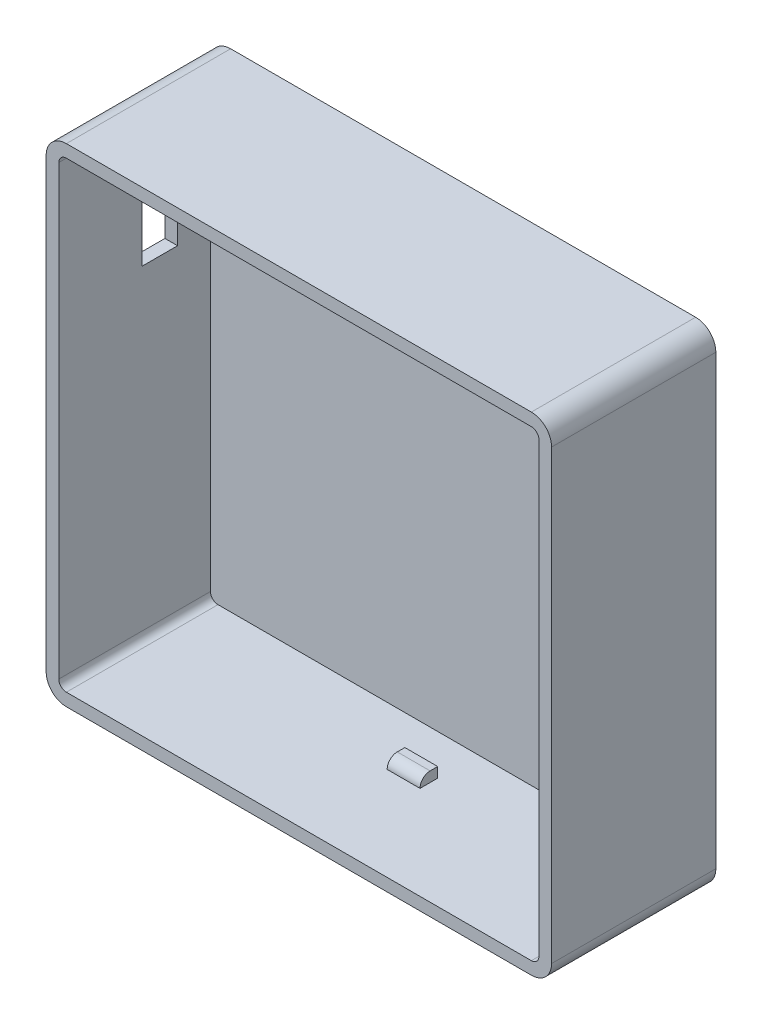
SolidWorks part; units mm, degrees
ref_plane "Front Plane" through (0, 0, 0) normal (0, 0, 1) x (1, 0, 0)
ref_plane "Top Plane" through (0, 0, 0) normal (0, 1, 0) x (1, 0, 0)
ref_plane "Right Plane" through (0, 0, 0) normal (1, 0, 0) x (0, 0, -1)
sketch "Sketch1" plane through (0, 0, 0) normal (0, 0, 1) x (1, 0, 0)
  line L1 (0, 0) -> (50.8, 0)
  line L2 (0, 0) -> (0, 49.022)
  line L3 (0, 49.022) -> (50.8, 49.022)
  line L4 (50.8, 0) -> (50.8, 49.022)
  dimension "D1" = 49.022
  dimension "D2" = 50.8
extrude "Boss-Extrude2" add sketch "Sketch1" along normal blind 16.51 contours L3 L4 L1 L2
fillet "Fillet1" radius 2.032 4 edges at (50.8, 0, 8.255) (50.8, 49.022, 8.255) (0, 0, 8.255) (0, 49.022, 8.255)
shell "Shell2" thickness 1.27 removed face at (25.4, 24.511, 16.51)
sketch "Sketch4" plane through (0, 0, 0) normal (-1, 0, 0) x (0, 0, 1)
  line L0 (0, 2.032) -> (16.51, 2.032) construction
  line L1 (8.128, 43.942) -> (4.572, 43.942)
  line L2 (8.128, 43.942) -> (8.128, 33.782)
  line L3 (8.128, 33.782) -> (4.572, 33.782)
  line L4 (4.572, 43.942) -> (4.572, 33.782)
  line L5 (16.51, 1.27) -> (1.27, 1.27) construction
  line L6 (16.51, 46.99) -> (0, 46.99) construction
  line L7 (16.51, 0) -> (0, 0) construction
  line L8 (1.27, 47.752) -> (16.51, 47.752) construction
  line L9 (16.51, 46.99) -> (1.27, 46.99) construction
  line L10 (0, 2.032) -> (0, 46.99) construction
  point P15 (8.89, 47.752)
  dimension "D1" = 10.16
  dimension "D2" = 3.556
  dimension "D3" = 31.75
  dimension "D4" = 3.048
  dimension "D5" = 2.032
  dimension "D6" = 0.762
  dimension "D7" = 0.762
  dimension "D8" = 8.128
  dimension "D9" = 4.572
extrude "Cut-Extrude2" cut sketch "Sketch4" against normal blind 1.27
sketch "Sketch7" plane through (0, 49.022, 0) normal (0, 1, 0) x (1, 0, 0)
  line L1 (21.4695, -5.334) -> (24.7216, -5.334)
  line L2 (21.4695, -5.334) -> (21.4695, -7.2375)
  line L3 (21.4695, -7.2375) -> (24.7216, -7.2375)
  line L4 (24.7216, -5.334) -> (24.7216, -7.2375)
  line L5 (2.032, 0) -> (48.768, 0) construction
  point P4 (24.7216, -6.1482)
  dimension "D1" = 5.334
  dimension "D2" = 3.2521
extrude "Boss-Extrude5" add sketch "Sketch7" against normal blind 2.286
fillet "Fillet6" radius 1.016 1 edges at (23.0955, 46.736, 7.2375) type face fillet first side face at (23.0955, 46.736, 6.2857) second side face at (23.0955, 47.244, 7.2375)
sketch "Sketch8" plane through (50.8, 0, 0) normal (1, 0, 0) x (0, 0, -1)
  line L0 (0, 2.032) -> (0, 46.99) construction
  line L1 (-7.112, 27.6643) -> (-5.334, 27.6643)
  line L2 (-7.112, 27.6643) -> (-7.112, 24.3623)
  line L3 (-7.112, 24.3623) -> (-5.334, 24.3623)
  line L4 (-5.334, 27.6643) -> (-5.334, 24.3623)
  dimension "D1" = 3.302
  dimension "D2" = 1.778
  dimension "D3" = 5.334
sketch "Sketch5" plane through (0, 47.752, 0) normal (0, -1, 0) x (1, 0, 0)
  line L0 (2.032, 1.27) -> (48.768, 1.27) construction
  line L3 (26.3069, 6.35) -> (21.4081, 6.35)
  point P6 (35.4884, 8.3964)
  point P7 (23.8575, 6.35)
  line B0 (26.3069, 8.3964) -> (21.4081, 8.3964)
  line B1 (26.3069, 8.3964) -> (26.3069, 6.35)
  line B2 (21.4081, 8.3964) -> (21.4081, 6.35)
  dimension "D1" = 5.08
sketch_block_instance "Block2-1"
sketch_block "Block2"
extrude "Boss-Extrude6" add sketch "Sketch8" against normal blind 2.286
fillet "Fillet7" radius 1.016 1 edges at (48.514, 26.0133, 7.112) type face fillet first side face at (48.514, 26.0133, 6.223) second side face at (49.022, 26.0133, 7.112)
sketch "Sketch9" plane through (0, 0, 0) normal (0, -1, 0) x (1, 0, 0)
  line L0 (2.032, 0) -> (48.768, 0) construction
  line L1 (24.8754, 7.112) -> (28.1774, 7.112)
  line L2 (24.8754, 7.112) -> (24.8754, 5.334)
  line L3 (24.8754, 5.334) -> (28.1774, 5.334)
  line L4 (28.1774, 7.112) -> (28.1774, 5.334)
  point P6 (31.0358, 7.112)
  point P7 (28.1774, 7.112)
  dimension "D1" = 1.778
  dimension "D2" = 3.302
  dimension "D3" = 5.334
extrude "Boss-Extrude7" add sketch "Sketch9" against normal blind 2.286
fillet "Fillet8" radius 1.016 1 edges at (26.5264, 2.286, 7.112) type face fillet first side face at (26.5264, 2.286, 6.223) second side face at (26.5264, 1.778, 7.112)
